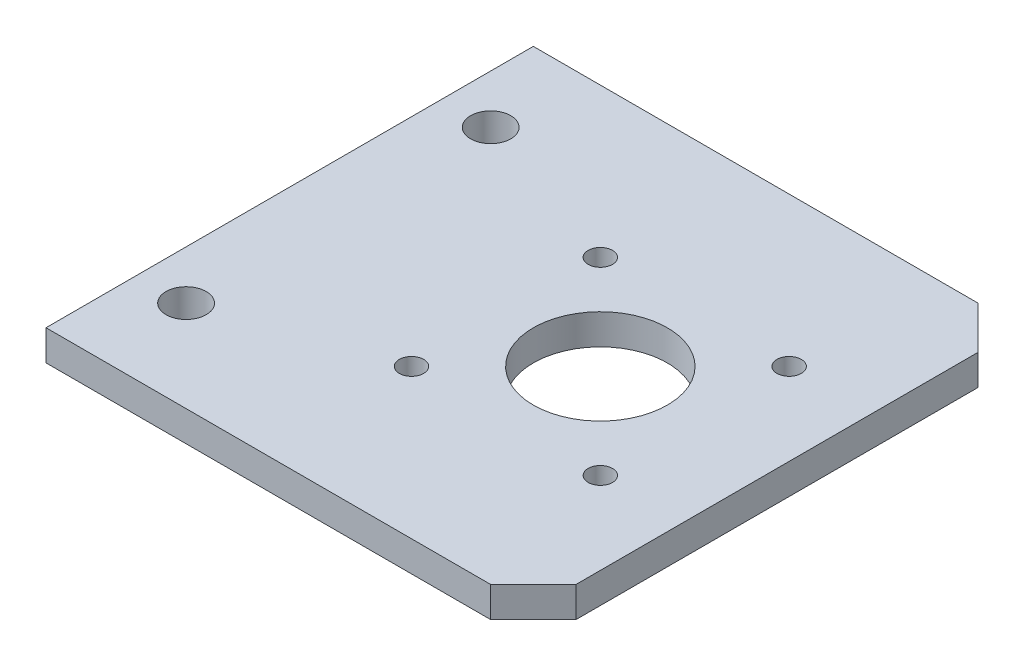
SolidWorks part; units mm, degrees
material "6063-T5"
ref_plane "Piano frontale" through (0, 0, 0) normal (0, 0, 1) x (1, 0, 0)
ref_plane "Piano superiore" through (0, 0, 0) normal (0, 1, 0) x (1, 0, 0)
ref_plane "Piano destro" through (0, 0, 0) normal (1, 0, 0) x (0, 0, -1)
sketch "Schizzo1" plane through (0, 0, 0) normal (0, 0, 1) x (1, 0, 0)
  line L1 (0, 0) -> (80, 0)
  line L2 (0, 0) -> (0, 5)
  line L3 (0, 5) -> (80, 5)
  line L4 (80, 0) -> (80, 5)
  dimension "D1" = 5
  dimension "D2" = 80
extrude "Estrusione-Estrusione1" add sketch "Schizzo1" along normal blind 80
hole_wizard "Foro per Vite M6-1" positions "Schizzo3" profile "Schizzo2" hole size "M6" standard "ISO" end condition through all
sketch "Schizzo3" plane through (0, 5, 0) normal (0, 1, 0) x (1, 0, 0)
  line L0 (-9.8996, -40) -> (95.021, -40) construction
  line L2 (80, -80) -> (0, -80) construction
  line L3 (80, 0) -> (0, 0) construction
  line L4 (0, -80) -> (0, 0) construction
  point P0 (8, -15)
  point P1 (8, -65)
  dimension "D1" = 15
  dimension "D2" = 8
sketch "Schizzo2" plane through (8, 5, 15) normal (1, 0, 0) x (0, 0, 1)
  line L0 (0, 0) -> (0, 5)
  line L1 (0, 5) -> (3.3, 5)
  line L2 (3.3, 5) -> (3.3, 0)
  line L5 (3.3, 0) -> (0, 0)
  line L11 (0, -6.35) -> (0, 107.95) construction
  dimension "Thru Hole Dia." = 6.6
  dimension "Thru Hole Depth" = 5
sketch "Schizzo4" plane through (0, 5, 0) normal (0, 1, 0) x (1, 0, 0)
  line L3 (19.8289, -40) -> (54.8798, -40) construction
  line L4 (80, -80) -> (0, -80) construction
  line L5 (80, 0) -> (0, 0) construction
  circle A0 centre (51, -40) radius 11
  circle A1 centre (8, -15) radius 3.3 construction
  dimension "D1" = 22
  dimension "D2" = 43
extrude "Taglio-Estrusione1" cut sketch "Schizzo4" against normal through all
sketch "Schizzo6" plane through (0, 5, 0) normal (0, 1, 0) x (1, 0, 0)
  line L0 (42.0101, -40) -> (55.783, -40) construction
  line L1 (51, -40) -> (51, -30.1482) construction
  line L2 (80, -80) -> (0, -80) construction
  line L3 (80, 0) -> (0, 0) construction
  circle A0 centre (35.5, -24.5) radius 2
  circle A1 centre (66.5, -24.5) radius 2
  circle A2 centre (66.5, -55.5) radius 2
  circle A3 centre (35.5, -55.5) radius 2
  dimension "D1" = 4
  dimension "D2" = 31
  dimension "D3" = 31
  dimension "D4" = 15.5
extrude "Taglio-Estrusione3" cut sketch "Schizzo6" against normal through all
chamfer "Chamfer1" distance 7 angle 45 2 edges at (80, 2.5, 0) (80, 2.5, 80)
